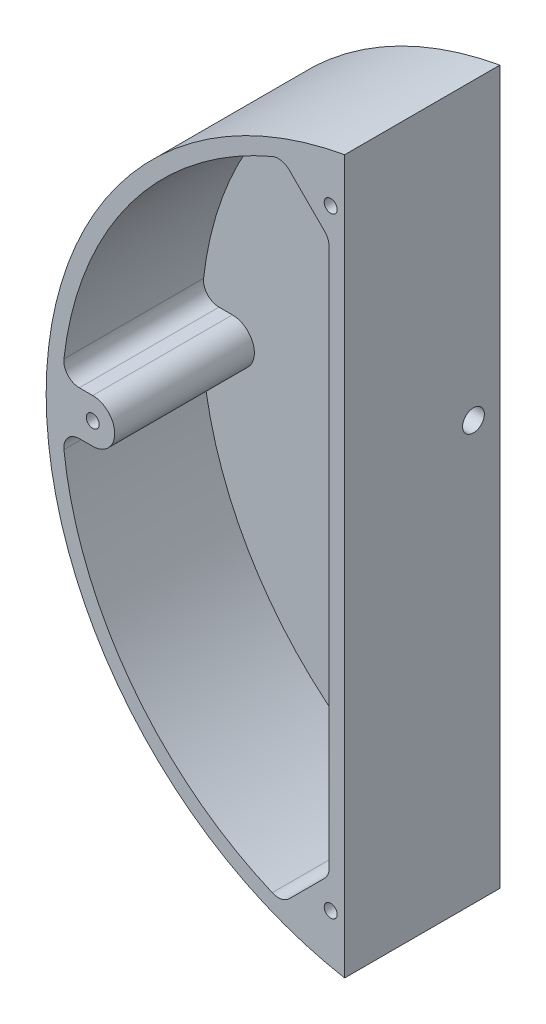
SolidWorks part; units mm, degrees
ref_plane "Front Plane" through (0, 0, 0) normal (0, 0, 1) x (1, 0, 0)
ref_plane "Top Plane" through (0, 0, 0) normal (0, 1, 0) x (1, 0, 0)
ref_plane "Right Plane" through (0, 0, 0) normal (1, 0, 0) x (0, 0, -1)
sketch "Sketch1" plane through (0, 0, 0) normal (0, 0, 1) x (1, 0, 0)
  line L0 (-12.3, -68.9109) -> (-12.3, 68.9109)
  line L1 (-15, 59) -> (-15, -59) construction
  line L5 (-61, 0) -> (0, 0) construction
  circle A2 centre (-15, 59) radius 1.25
  circle A4 centre (-61, 0) radius 1.25
  circle A5 centre (-15, -59) radius 1.25
  arc A6 (-12.3, 68.9109) -> (-12.3, -68.9109) centre (0, 0) ccw
  circle A7 centre (0, 0) radius 65.5 construction
  circle A8 centre (-15, 59) radius 3 construction
  circle A9 centre (-61, 0) radius 3 construction
  circle A10 centre (-15, -59) radius 3 construction
  point P6 (-15, 0)
  dimension "D2" = 2.5
  dimension "D6" = 118
  dimension "D7" = 131
  dimension "D8" = 2.5
  dimension "D4" = 70
  dimension "D3" = 2.5
  dimension "D10" = 6
  dimension "D1" = 12.3
  dimension "D5" = 15
  dimension "D9" = 61
extrude "Boss-Extrude2" add sketch "Sketch1" along normal blind 30
shell "Shell1" thickness 3 removed face at (-13.75, 59, 30)
sketch "Sketch10" plane through (0, 0, 3) normal (0, 0, 1) x (1, 0, 0)
  line L0 (-15.3, 53.2896) -> (-24.4068, 62.3964)
  line L1 (-15.3, -54.7606) -> (-15.3, 54.7606) construction
  line L2 (-15.3, -53.2896) -> (-24.4068, -62.3964)
  line L3 (-15.3, -54.7606) -> (-15.3, 54.7606) construction
  line L4 (-15.3, 65.2297) -> (-15.3, 60.2135)
  line L5 (-15.3, 57.7865) -> (-15.3, 53.2896)
  line L6 (-15.3, 63.2394) -> (-15.3, 65.2297) construction
  line L7 (-15.3, -65.2297) -> (-15.3, -60.2135)
  line L8 (-15.3, -57.7865) -> (-15.3, -53.2896)
  line L9 (-61, -4.25) -> (-63.588, -4.25)
  line L10 (-61, 4.25) -> (-63.588, 4.25)
  arc A0 (-24.4068, 62.3964) -> (-15.3, 65.2297) centre (0, 0) cw
  arc A1 (-63.588, -4.25) -> (-66.5687, -7.5898) centre (-63.588, -7.25) ccw
  arc A2 (-15.3, 65.2297) -> (-15.3, -65.2297) centre (0, 0) ccw construction
  arc A3 (-15.3, 65.2297) -> (-15.3, -65.2297) centre (0, 0) ccw construction
  arc A4 (-15.3, -54.7606) -> (-15.3, -63.2394) centre (-15, -59) ccw construction
  arc A5 (-15.3, 63.2394) -> (-15.3, 54.7606) centre (-15, 59) ccw construction
  arc A6 (-15.3, -65.2297) -> (-24.4068, -62.3964) centre (0, 0) cw
  circle A7 centre (-15, 59) radius 1.25 construction
  arc A8 (-15.3, 60.2135) -> (-15.3, 57.7865) centre (-15, 59) ccw
  circle A9 centre (-15, -59) radius 1.25 construction
  arc A10 (-15.3, -60.2135) -> (-15.2655, -57.7785) centre (-15, -59) cw
  arc A11 (-61, 4.25) -> (-61, -4.25) centre (-61, 0) cw
  circle A12 centre (-61, 0) radius 4.25 construction
  circle A13 centre (-61, 0) radius 4.25 construction
  arc A14 (-63.588, 4.25) -> (-66.5687, 7.5898) centre (-63.588, 7.25) cw
  arc A15 (-66.5687, 7.5898) -> (-66.5687, -7.5898) centre (0, 0) ccw
  circle A16 centre (-61, 0) radius 1.25
  point P57 (-66.8651, 4.25)
  line M8 (-15.3, 63.2394) -> (-15.3, 65.2297)
  arc M9 (-15.3, 65.2297) -> (-15.3, -65.2297) centre (0, 0) ccw
  line M10 (-15.3, -65.2297) -> (-15.3, -63.2394)
  arc M11 (-15.3, -63.2394) -> (-15.3, -54.7606) centre (-15, -59) cw
  line M12 (-15.3, -54.7606) -> (-15.3, 54.7606)
  arc M13 (-15.3, 54.7606) -> (-15.3, 63.2394) centre (-15, 59) cw
  circle M14 centre (-61, 0) radius 4.25
  dimension "D3" = 3
  dimension "D1" = 135
  dimension "D2" = 135
extrude "Boss-Extrude6" add sketch "Sketch10" along normal up to surface (27 mm away) contours L10 A14 A1 L9 M9 M14 | A16 M14 | L7 A10 L8 M11 | L2 M11 M9 M10 | L0 M13 M8 M9 | A8 L4 L5 M13 | L2 M12 M11 | L0 M12 M13 region at (-16.0191, 54.4613, 3) region at (-17.0571, 59, 3) region at (-19.7689, 61.9404, 3) region at (-16.0191, -54.4613, 3) region at (-19.7689, -61.9404, 3) region at (-17.0571, -59, 3) region at (-65.581, 0, 3) region at (-58.0798, 2.9202, 3) up to face at (-25.2333, 0, 30)
fillet "Fillet1" radius 3 4 edges at (-24.4068, -62.3964, 16.5) (-15.3, -53.2896, 16.5) (-15.3, 53.2896, 16.5) (-24.4068, 62.3964, 16.5)
sketch "Sketch11" plane through (-12.3, 0, 0) normal (1, 0, 0) x (0, 0, -1)
  line L0 (-3, -52.047) -> (-3, 52.047) construction
  circle A0 centre (-5.1, 12) radius 2.1
  dimension "D1" = 4.2
  dimension "D2" = 12
extrude "Cut-Extrude4" cut sketch "Sketch11" against normal blind 10
